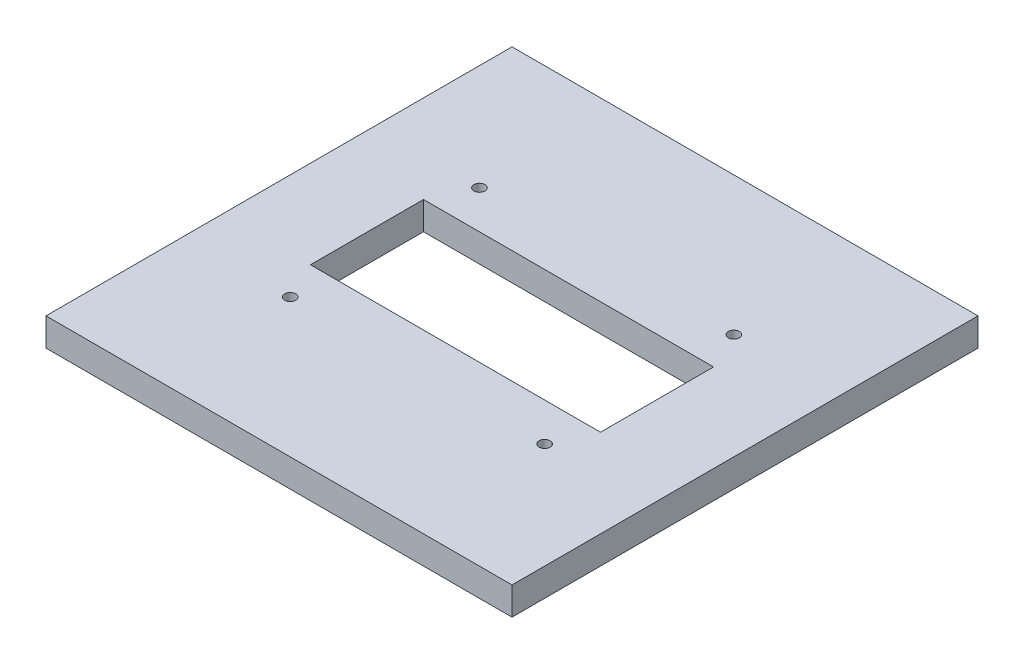
SolidWorks part; units mm, degrees
ref_plane "Plano frontal" through (0, 0, 0) normal (0, 0, 1) x (1, 0, 0)
ref_plane "Plano superior" through (0, 0, 0) normal (0, 1, 0) x (1, 0, 0)
ref_plane "Plano direito" through (0, 0, 0) normal (1, 0, 0) x (0, 0, -1)
sketch "Esboço1" plane through (0, 0, 0) normal (0, 1, 0) x (1, 0, 0)
  line L1 (0, 0) -> (50, 0)
  line L2 (0, 0) -> (0, 50)
  line L3 (0, 50) -> (50, 50)
  line L4 (50, 0) -> (50, 50)
  dimension "D1" = 50
  dimension "D2" = 50
extrude "Base" add sketch "Esboço1" along normal blind 3
sketch "posicaoSensor" plane through (0, 3, 0) normal (0, 1, 0) x (1, 0, 0)
  line L0 (9.44, 37.065) -> (9.44, 12.935) construction
  line L1 (9.44, 12.935) -> (40.56, 12.935) construction
  line L2 (40.56, 12.935) -> (40.56, 37.065) construction
  line L3 (40.56, 37.065) -> (9.44, 37.065) construction
  line L4 (50, 50) -> (0, 50) construction
  line L5 (50, 0) -> (50, 50) construction
  point P4 (25, 37.065)
  point P7 (25, 50)
  point P10 (50, 25)
  point P11 (40.56, 25)
  dimension "D1" = 24.13
  dimension "D2" = 31.12
sketch "EntradasEsb" plane through (0, 3, 0) normal (0, 1, 0) x (1, 0, 0)
  line L1 (9.44, 18.935) -> (40.56, 18.935)
  line L6 (9.44, 31.065) -> (40.56, 31.065)
  line L8 (40.56, 12.935) -> (40.56, 37.065) construction
  line L9 (9.44, 31.065) -> (9.44, 18.935)
  line L10 (40.56, 18.935) -> (40.56, 31.065)
  line L11 (40.56, 37.065) -> (9.44, 37.065) construction
  line L12 (9.44, 12.935) -> (40.56, 12.935) construction
  line L13 (9.44, 37.065) -> (9.44, 12.935) construction
  circle A0 centre (11.35, 35.155) radius 0.595
  circle A1 centre (38.65, 35.155) radius 0.595
  circle A2 centre (38.65, 14.845) radius 0.595
  circle A3 centre (11.35, 14.845) radius 0.595
  point P8 (0, 0)
  point P9 (0, 0)
  point P19 (0, 0)
  point P20 (0, 0)
  point P21 (0, 0)
  dimension "D4" = 1.19
  dimension "D7" = 1.91
  dimension "D1" = 12.13
  dimension "D2" = 31.12
  dimension "D3" = 6
  dimension "D5" = 1.91
  dimension "D6" = 1.91
  dimension "D8" = 1.91
extrude "Corte-extrusão1" cut sketch "EntradasEsb" against normal blind 3
